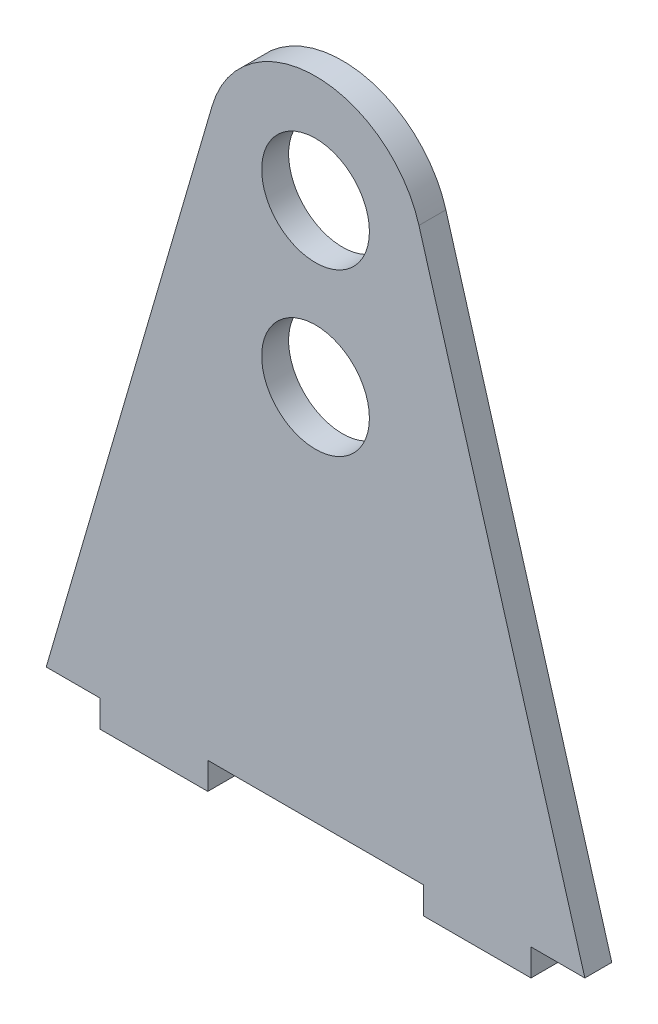
SolidWorks part; units mm, degrees
material "Pine"
ref_plane "Front Plane" through (0, 0, 0) normal (0, 0, 1) x (1, 0, 0)
ref_plane "Top Plane" through (0, 0, 0) normal (0, 1, 0) x (1, 0, 0)
ref_plane "Right Plane" through (0, 0, 0) normal (1, 0, 0) x (0, 0, -1)
sketch "Sketch1" plane through (0, 0, 0) normal (0, 0, 1) x (1, 0, 0)
  line L0 (0, 0) -> (0, 127) construction
  line L1 (25.4, 0) -> (-25.4, 0)
  line L2 (-25.4, 0) -> (-25.4, -6.35)
  line L3 (-25.4, -6.35) -> (-50.8, -6.35)
  line L4 (-50.8, -6.35) -> (-50.8, 0)
  line L5 (-50.8, 0) -> (-63.5, 0)
  line L6 (-63.5, 0) -> (-24.384, 134.112)
  line L7 (0, 127) -> (0, 159.1888) construction
  line L8 (50.8, 0) -> (63.5, 0)
  line L9 (50.8, -6.35) -> (50.8, 0)
  line L10 (25.4, 0) -> (25.4, -6.35)
  line L11 (25.4, -6.35) -> (50.8, -6.35)
  line L12 (63.5, 0) -> (24.384, 134.112)
  arc A0 (24.384, 134.112) -> (-24.384, 134.112) centre (0, 127) ccw
  circle A1 centre (0, 127) radius 12.7
  circle A2 centre (0, 88.9) radius 12.7
  dimension "D5" = 12.7
  dimension "D7" = 25.4
  dimension "D8" = 25.4
  dimension "D1" = 63.5
  dimension "D2" = 6.35
  dimension "D3" = 25.4
  dimension "D4" = 25.4
  dimension "D6" = 127
  dimension "D9" = 38.1
extrude "Boss-Extrude1" add sketch "Sketch1" along normal blind 6.35
